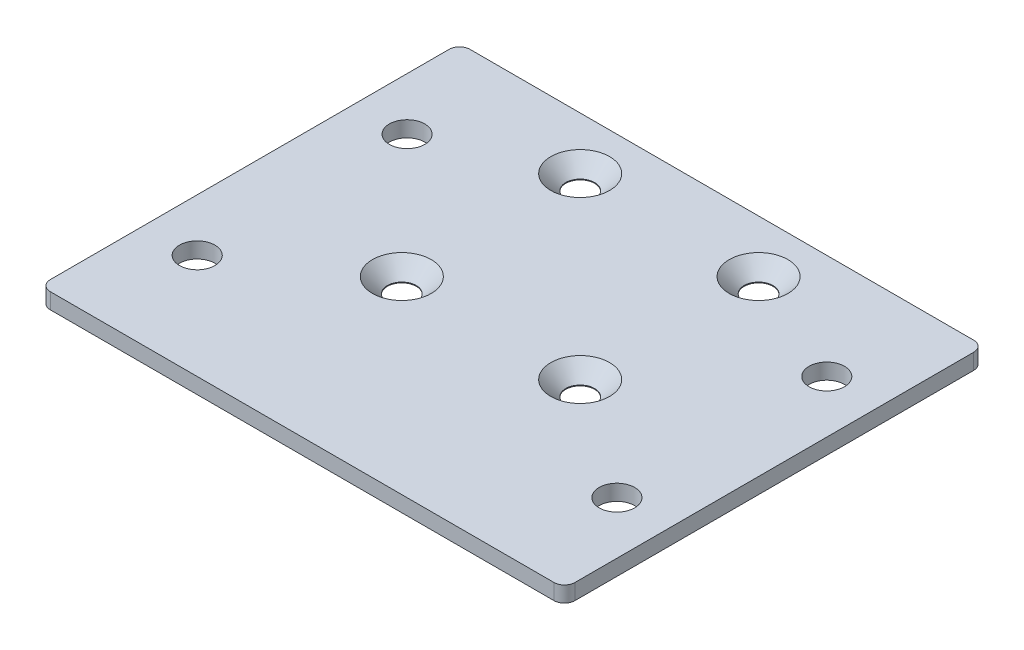
SolidWorks part; units mm, degrees
note: The reader was unsure of these and kept them because the rebuilt part matched: thickness of "Brida base1", "Chapa metálica1", "Chapa metálica2", "Chapa metálica3".
ref_plane "Alzado" through (0, 0, 0) normal (0, 0, 1) x (1, 0, 0)
ref_plane "Planta" through (0, 0, 0) normal (0, 1, 0) x (1, 0, 0)
ref_plane "Vista lateral" through (0, 0, 0) normal (1, 0, 0) x (0, 0, -1)
sketch "Croquis1" plane through (0, 0, 0) normal (0, 1, 0) x (1, 0, 0)
  line L1 (-149.7778, 34.4444) -> (-49.7778, 34.4444)
  line L2 (-149.7778, 34.4444) -> (-149.7778, -45.5556)
  line L3 (-149.7778, -45.5556) -> (-49.7778, -45.5556)
  line L4 (-49.7778, 34.4444) -> (-49.7778, -45.5556)
  dimension "130" = 100
  dimension "D2" = 80
base flange "Brida base1" sketch "Croquis1" thickness 3 reverse thickness direction no parameters "D1"=10
fillet "Redondeo1" radius 2 4 edges at (-149.7778, -1.5, -34.4444) (-49.7778, -1.5, -34.4444) (-49.7778, -1.5, 45.5556) (-149.7778, -1.5, 45.5556)
hole_wizard "Taladro de margen para 1/41" positions "Croquis7" profile "Croquis6" hole size "1/4" standard "Ansi Inch" end condition through all
sketch "Croquis7" plane through (0, 0, 0) normal (0, 1, 0) x (1, 0, 0)
  line L0 (-149.7778, 32.4444) -> (-149.7778, -43.5556) construction
  line L11 (-149.7778, -5.5556) -> (-49.7778, -5.5556) construction
  line L12 (-49.7778, -43.5556) -> (-49.7778, 32.4444) construction
  point P2 (-139.7778, -25.5556)
  point P4 (-59.7778, -25.5556)
  point P66 (-139.7778, 14.4444)
  point P68 (-59.7778, 14.4444)
  dimension "D1" = 80
  dimension "D2" = 20
  dimension "D3" = 20
  dimension "15" = 10
sketch "Croquis6" plane through (-139.7778, 0, 25.5556) normal (1, 0, 0) x (0, 0, 1)
  line L0 (0, 0) -> (0, 3)
  line L1 (0, 3) -> (3.3782, 3)
  line L2 (3.3782, 3) -> (3.3782, 0)
  line L5 (3.3782, 0) -> (0, 0)
  line L11 (0, -6.35) -> (0, 107.95) construction
  dimension "Diámetro de taladro hasta el siguiente" = 6.7564
  dimension "Profundidad de taladro hasta el siguiente" = 3
sketch "Croquis8" plane through (0, 0, 0) normal (0, 1, 0) x (1, 0, 0)
  line L0 (-149.7778, -5.5556) -> (-49.7778, -5.5556) construction
  line L1 (-149.7778, 32.4444) -> (-149.7778, -43.5556) construction
  line L2 (-49.7778, -43.5556) -> (-49.7778, 32.4444) construction
  line L3 (-99.7778, 34.4444) -> (-99.7778, -45.5556) construction
  line L4 (-51.7778, 34.4444) -> (-147.7778, 34.4444) construction
  line L5 (-147.7778, -45.5556) -> (-51.7778, -45.5556) construction
hole_wizard "Refrentado para tornillo tapón con cabeza plana de clavija de M51" positions "Croquis10" profile "Croquis9" countersink size "M5" standard "Ansi Metric" end condition through all
sketch "Croquis10" plane through (0, 0, 0) normal (0, 1, 0) x (1, 0, 0)
  line L2 (-99.7778, 34.4444) -> (-99.7778, -45.5556) construction
  line L4 (-51.7778, 34.4444) -> (-147.7778, 34.4444) construction
  point P0 (-116.7778, 24.4444)
  point P2 (-82.7778, 24.4444)
  point P4 (-82.7778, -9.5556)
  point P6 (-116.7778, -9.5556)
  dimension "D1" = 34
  dimension "D2" = 34
  dimension "D3" = 17
  dimension "D4" = 10
sketch "Croquis9" plane through (-116.7778, 0, -24.4444) normal (1, 0, 0) x (0, 0, 1)
  line L0 (0, 0) -> (0, 3)
  line L1 (0, 3) -> (2.75, 3)
  line L2 (2.75, 3) -> (2.75, 2.85)
  line L3 (2.75, 2.85) -> (5.6, 0)
  line L5 (5.6, 0) -> (0, 0)
  line L6 (-2.75, 2.85) -> (-5.6, 0) construction
  line L11 (0, -6.35) -> (0, 107.95) construction
  dimension "Diámetro de taladro hasta el siguiente" = 5.5
  dimension "Profundidad de taladro hasta el siguiente" = 3
  dimension "Diámetro de avellanado cercano" = 11.2
  dimension "Ángulo de avellanado cercano" = 90
sketch "Líneas de pliegue1" [suppressed] plane through (0, 0, 0) normal (0, 1, 0) x (1, 0, 0)
sketch "Cuadro delimitador1" [suppressed] plane through (0, 0, 0) normal (0, 1, 0) x (1, 0, 0)
sheet metal parameters "Chapa metálica1" thickness 3 parameters "D1"=10
flat pattern "Chapa desplegada1" [suppressed]
sketch "Líneas de pliegue2" plane through (0, 0, 0) normal (0, 1, 0) x (1, 0, 0)
sketch3d "Cuadro delimitador2" [suppressed]
  line L0 (-149.7778, -45.5554, 0) -> (110.2222, -45.5556, 0) construction
  line L1 (-149.7777, 34.4444, 0) -> (110.2223, 34.4443, 0) construction
  line L2 (-149.7778, -45.5554, 0) -> (-149.7777, 34.4444, 0) construction
  line L3 (110.2222, -45.5556, 0) -> (110.2223, 34.4443, 0) construction
sheet metal parameters "Chapa metálica2" thickness 3 parameters "D1"=10, "D7"=6.35
flat pattern "Chapa desplegada1"
sketch "Líneas de pliegue2" plane through (0, 0, 0) normal (0, 1, 0) x (1, 0, 0)
sketch3d "Cuadro delimitador2" [suppressed]
  line L0 (-149.7778, -85.5554, 0) -> (110.2222, -85.5556, 0) construction
  line L1 (-149.7777, 34.4444, 0) -> (110.2223, 34.4443, 0) construction
  line L2 (-149.7778, -85.5554, 0) -> (-149.7777, 34.4444, 0) construction
  line L3 (110.2222, -85.5556, 0) -> (110.2223, 34.4443, 0) construction
sheet metal parameters "Chapa metálica3" thickness 3 parameters "D1"=10, "D7"=6.35
flat pattern "Chapa desplegada1"
sketch "Líneas de pliegue2" plane through (0, 0, 0) normal (0, 1, 0) x (1, 0, 0)
sketch3d "Cuadro delimitador2" [suppressed]
  line L0 (-149.7778, -45.5555, 0) -> (-49.7778, -45.5556, 0) construction
  line L1 (-149.7777, 34.4444, 0) -> (-49.7777, 34.4444, 0) construction
  line L2 (-149.7778, -45.5555, 0) -> (-149.7777, 34.4444, 0) construction
  line L3 (-49.7778, -45.5556, 0) -> (-49.7777, 34.4444, 0) construction
